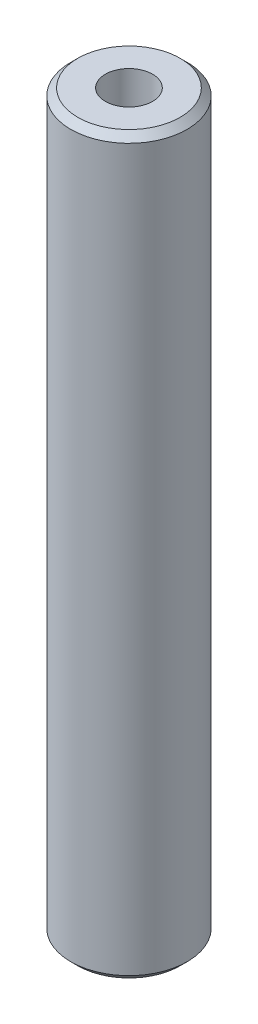
SolidWorks part; units mm, degrees
ref_plane "Front Plane" through (0, 0, 0) normal (0, 0, 1) x (1, 0, 0)
ref_plane "Top Plane" through (0, 0, 0) normal (0, 1, 0) x (1, 0, 0)
ref_plane "Right Plane" through (0, 0, 0) normal (1, 0, 0) x (0, 0, -1)
sketch "Sketch1" plane through (0, 0, 0) normal (0, 1, 0) x (1, 0, 0)
  circle A0 centre (0, 0) radius 47.5
  dimension "SHAFT_OD" = 95
extrude "Boss-Extrude1" add sketch "Sketch1" along normal blind 600
sketch "Sketch2" plane through (0, 0, 0) normal (0, 1, 0) x (1, 0, 0)
  circle A0 centre (0, 0) radius 19.2793
  dimension "BORE_D" = 38.5586
extrude "Cut-Extrude1" cut sketch "Sketch2" along normal through all
chamfer "Chamfer1" distance 5.6977 angle 45 2 edges at (0, 600, 47.5) (0, 0, 47.5)
